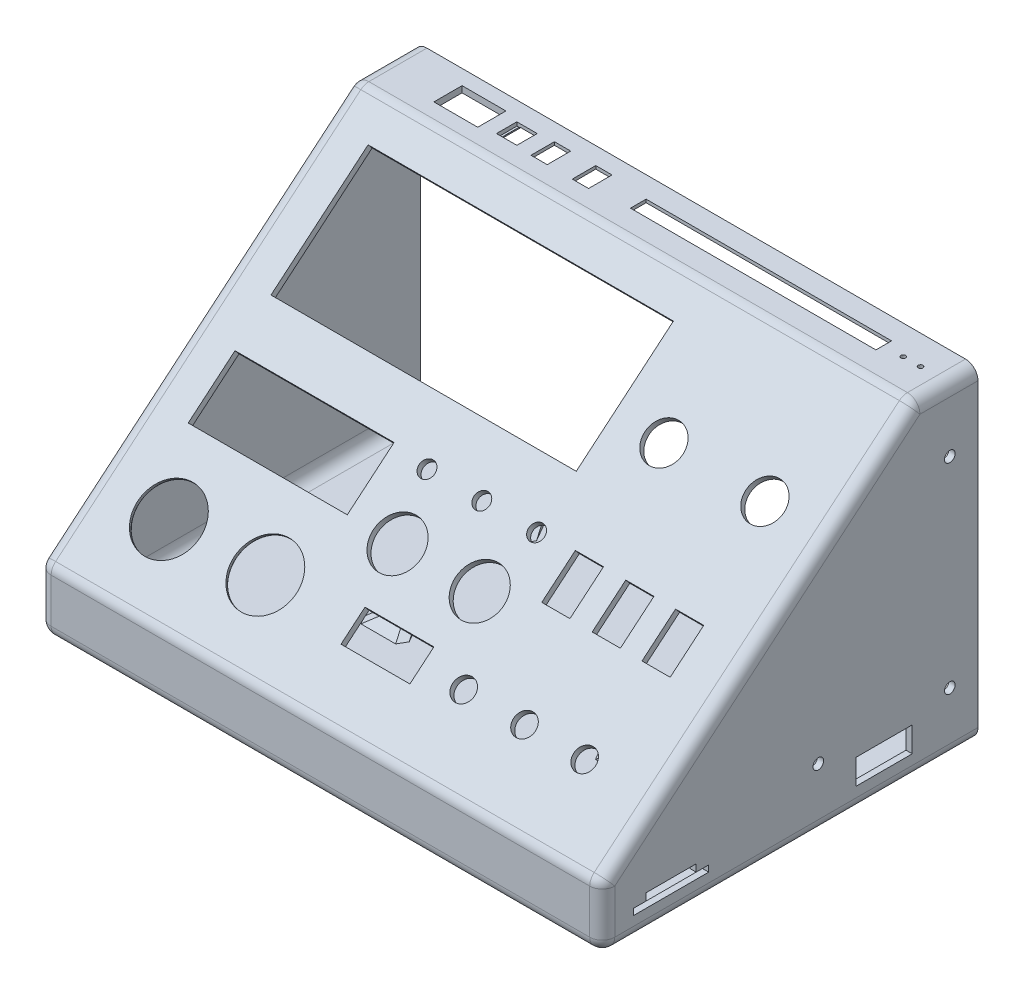
SolidWorks part; units mm, degrees
ref_plane "Front Plane" through (0, 0, 0) normal (0, 0, 1) x (1, 0, 0)
ref_plane "Top Plane" through (0, 0, 0) normal (0, 1, 0) x (1, 0, 0)
ref_plane "Right Plane" through (0, 0, 0) normal (1, 0, 0) x (0, 0, -1)
sketch "Sketch1" plane through (0, 0, 0) normal (0, 1, 0) x (1, 0, 0)
  line L1 (-90, -60) -> (90, -60)
  line L2 (-90, -60) -> (-90, 60)
  line L3 (-90, 60) -> (90, 60)
  line L4 (90, -60) -> (90, 60)
  line L5 (-90, -60) -> (90, 60) construction
  line L6 (-90, 60) -> (90, -60) construction
  point P0 (0, 0)
  dimension "D1" = 180
  dimension "D2" = 120
extrude "Boss-Extrude1" add sketch "Sketch1" along normal blind 20
sketch "Sketch2" plane through (-90, 0, 0) normal (-1, 0, 0) x (0, 0, 1)
  line L0 (60, 20) -> (-40, 103.91)
  line L1 (-60, 20) -> (60, 20) construction
  line L2 (60, 20) -> (60, 0) construction
  line L3 (-60, 20) -> (-60, 103.91)
  line L4 (-60, 103.91) -> (-40, 103.91)
  line L5 (-60, 20) -> (60, 20)
  dimension "D1" = 40
  dimension "D2" = 100
extrude "Boss-Extrude2" add sketch "Sketch2" against normal up to surface (180 mm away) up to face at (90, 10, 0)
shell "Shell3" thickness 2 removed face at (0, 51.955, -60)
fillet "Fillet1" radius 4 11 edges at (-90, 10, 60) (90, 10, 60) (0, 0, 60) (0, 20, 60) (-90, 61.955, 10) (0, 103.91, -40) (90, 61.955, 10) (-90, 103.91, -50) (-90, 0, 0) (90, 0, 0) (90, 103.91, -50)
fillet "Fillet2" radius 4 11 edges at (88, 10.5337, 58) (0, 19.0674, 58) (-88, 10.5337, 58) (0, 2, 58) (88, 101.91, -50.364) (0, 101.91, -40.7279) (-88, 101.91, -50.364) (88, 60.4887, 8.636) (88, 2, -1) (-88, 60.4887, 8.636) (-88, 2, -1)
sketch "Sketch7" plane through (0, 103.91, 0) normal (0, 1, 0) x (1, 0, 0)
  line L0 (-86, 60) -> (-86, 41.4559) construction
  line L1 (-86, 41.4559) -> (-86, 50.7279) construction
  line L2 (-86, 50.7279) -> (-56, 50.7279) construction
  line L3 (-56, 46.2279) -> (-56, 55.2279)
  line L4 (-56, 55.2279) -> (-70, 55.2279)
  line L5 (-70, 55.2279) -> (-70, 46.2279)
  line L6 (-70, 46.2279) -> (-56, 46.2279)
  point P9 (-56, 50.7279)
  dimension "D1" = 9
  dimension "D2" = 14
  dimension "D3" = 30
extrude "Cut-Extrude3" cut sketch "Sketch7" against normal up to next
sketch "Sketch8" plane through (0, 41.2807, 34.6386) normal (0, 0.766, 0.6428) x (1, 0, 0)
  line L0 (-86, 95.9779) -> (86, 95.9779) construction
  line L1 (86, 95.9779) -> (86, -31.2417) construction
  line L2 (86, -31.2417) -> (-86, -31.2417) construction
  line L3 (-86, -31.2417) -> (-86, 95.9779) construction
  line L4 (-76, 95.9779) -> (-76, -31.2417)
  line L5 (-86, 85.9779) -> (86, 85.9779)
  line L6 (86, -31.2417) -> (86, 95.9779) construction
  line L7 (-86, -31.2417) -> (86, -31.2417) construction
  line L8 (76, -31.2417) -> (76, 95.9779)
  line L9 (86, -21.2417) -> (-86, -21.2417)
  line L10 (-86, 95.9779) -> (-86, -31.2417) construction
  line L11 (86, 95.9779) -> (-86, 95.9779) construction
  line L12 (-73.5, 95.9779) -> (-73.5, 93.4779)
  line L13 (-76, 85.9779) -> (21.5, 85.9779)
  line L14 (-76, 85.9779) -> (-76, 45.4779)
  line L15 (-76, 45.4779) -> (21.5, 45.4779)
  line L16 (21.5, 85.9779) -> (21.5, 45.4779)
  line L17 (-76, 85.9779) -> (21.5, 85.9779) construction
  line L18 (-27.25, 85.9779) -> (-27.25, 45.4779) construction
  line L19 (-45.177, 65.7279) -> (-9.323, 65.7279)
  circle A0 centre (-73.5, 93.4779) radius 1.35
  circle A1 centre (-73.5, 37.9779) radius 1.35
  circle A2 centre (19, 37.9779) radius 1.35
  circle A3 centre (19, 93.4779) radius 1.35
  point P36 (-27.25, 65.7279)
  dimension "D1" = 10
  dimension "D2" = 10
  dimension "D3" = 10
  dimension "D4" = 10
  dimension "D5" = 97.5
  dimension "D6" = 40.5
  dimension "D7" = 2.5
  dimension "D8" = 2.5
extrude "Boss-Extrude4" add sketch "Sketch8" against normal blind 5 contours A0 | A3 | A2 | A1
extrude "Cut-Extrude4" cut sketch "Sketch8<3>" against normal blind 5 contours L16 L5 L4 L15 region at (-27.25, 95.8676, -30.4155)
sketch "Sketch8<3>" plane through (0, 41.2807, 34.6386) normal (0, 0.766, 0.6428) x (1, 0, 0) same geometry as "Sketch8"
sketch "Sketch9" plane through (0, 41.2807, 34.6386) normal (0, 0.766, 0.6428) x (1, 0, 0)
  line L0 (-76, 85.9779) -> (-76, 30.4779)
  line L1 (-76, 45.4779) -> (21.5, 45.4779) construction
  line L3 (-76, 30.4779) -> (-25.2, 30.4779)
  line L4 (-76, 30.4779) -> (-76, 10.9779)
  line L5 (-76, 10.9779) -> (-25.2, 10.9779)
  line L6 (-25.2, 30.4779) -> (-25.2, 10.9779)
  dimension "D1" = 15
  dimension "D2" = 50.8
  dimension "D3" = 19.5
extrude "Cut-Extrude5" cut sketch "Sketch9" against normal blind 5 contours L6 L3 L4 L5 region at (-50.6, 54.6044, 18.7601)
sketch "Sketch10" plane through (0, 41.2807, 34.6386) normal (0, 0.766, 0.6428) x (1, 0, 0)
  line L0 (-25.2, 30.4779) -> (-25.2, 10.9779) construction
  line L1 (21.5, 45.4779) -> (21.5, 10.9779)
  line L2 (-25.2, 30.4779) -> (21.5, 30.4779) construction
  line L3 (21.5, 30.4779) -> (21.5, 10.9779) construction
  line L4 (21.5, 10.9779) -> (-25.2, 10.9779) construction
  line L5 (-13.525, 28.9779) -> (3.975, 28.9779)
  line L6 (3.975, 28.9779) -> (21.475, 28.9779)
  line L7 (3.975, 28.9779) -> (-13.525, 28.9779) construction
  line L8 (-13.525, 28.9779) -> (-4.775, 28.9779) construction
  line L9 (-4.775, 28.9779) -> (-13.525, 28.9779) construction
  line L10 (-13.525, 28.9779) -> (-9.15, 28.9779) construction
  line L11 (-9.15, 28.9779) -> (-9.15, 10.9779) construction
  line L12 (21.475, 28.9779) -> (3.975, 28.9779) construction
  line L13 (12.725, 28.9779) -> (21.475, 28.9779) construction
  line L14 (21.475, 28.9779) -> (17.1, 28.9779) construction
  line L15 (17.1, 28.9779) -> (17.1, 10.9779) construction
  circle A0 centre (3.975, 28.9779) radius 2.525
  circle A1 centre (-13.525, 28.9779) radius 2.525
  circle A2 centre (21.475, 28.9779) radius 2.525
  circle A3 centre (-9.15, 10.9779) radius 7.75
  circle A4 centre (17.1, 10.9779) radius 7.75
  point P7 (16.4524, 10.9779)
  point P22 (-10.0142, 10.9779)
  dimension "D1" = 18
  dimension "D2" = 35
  dimension "D3" = 17.5
extrude "Cut-Extrude6" cut sketch "Sketch10" against normal blind 5 contours A1 | A0 | A2 | A4 | A3 | A0 | A2 region at (17.1, 48.3372, 26.229) region at (-15.9786, 59.9074, 12.4402) region at (3.975, 59.2185, 13.2612) region at (21.4943, 59.9074, 12.4402) region at (-9.15, 48.3372, 26.229)
sketch "Sketch11" plane through (0, 41.2807, 34.6386) normal (0, 0.766, 0.6428) x (1, 0, 0)
  line L0 (21.5, 85.9779) -> (21.5, 45.4779) construction
  line L1 (86, 95.9779) -> (-86, 95.9779) construction
  line L2 (21.5, 65.7279) -> (86, 65.7279) construction
  line L3 (86, -31.2417) -> (86, 95.9779) construction
  line L4 (86, 65.7279) -> (53.75, 65.7279) construction
  line L5 (53.75, 65.7279) -> (21.5, 65.7279) construction
  line L6 (69.875, 67.1029) -> (69.875, 54.8529)
  line L7 (86, 65.7279) -> (53.75, 65.7279) construction
  line L8 (53.75, 65.7279) -> (86, 65.7279) construction
  line L9 (86, 65.7279) -> (69.875, 65.7279) construction
  line L10 (69.875, 65.7279) -> (69.875, 60.9779) construction
  line L11 (53.75, 65.7279) -> (53.75, 56.7637)
  circle A0 centre (69.875, 60.9779) radius 6.125
  circle A1 centre (37.625, 60.9779) radius 6.125
  dimension "D1" = 12.25
  dimension "D2" = 35
extrude "Cut-Extrude7" cut sketch "Sketch11" against normal blind 5 contours A1 | L6 A0 | L6 A0 region at (72.4745, 80.4766, -12.0732) region at (67.2755, 80.4766, -12.0732) region at (37.625, 80.4766, -12.0732)
sketch "Sketch12" plane through (0, 41.2807, 34.6386) normal (0, 0.766, 0.6428) x (1, 0, 0)
  line L0 (-76, 10.9779) -> (-76, -4.0221)
  line L1 (-76, -31.2417) -> (-76, -16.2417)
  line L2 (-86, -31.2417) -> (86, -31.2417) construction
  line L3 (-76, -4.0221) -> (-76, -16.2417) construction
  line L4 (-25.2, 10.9779) -> (-25.2, -31.2417)
  line L5 (-25.2, 30.4779) -> (-25.2, 10.9779) construction
  line L6 (-25.2, -31.2417) -> (-25.2, -10.1319)
  line L7 (-25.2, -10.1319) -> (-76, -10.1319)
  line L8 (-50.6, -10.1319) -> (-76, -10.1319) construction
  line L9 (-76, -10.1319) -> (-63.3, -10.1319) construction
  line L10 (-63.3, -10.1319) -> (-63.3, -2.7605) construction
  line L11 (-63.3, -2.7605) -> (-63.3, -10.1319) construction
  line L12 (-63.3, -10.1319) -> (-50.6, -10.1319) construction
  line L13 (-50.6, -10.1319) -> (-25.2, -10.1319) construction
  line L14 (-37.9, -10.1319) -> (-37.9, -2.7605) construction
  circle A2 centre (-66, -10.1319) radius 10
  circle A3 centre (-35.2, -10.1319) radius 10
  dimension "D1" = 15
  dimension "D2" = 15
extrude "Cut-Extrude8" cut sketch "Sketch12" against normal blind 5 contours L7 A2 | L7 A3 | L7 A3 | L7 A2 region at (-66, 32.04, 45.6513) region at (-35.2, 37.4961, 39.1489) region at (-35.2, 32.04, 45.6513) region at (-66, 37.4961, 39.1489)
fillet "Fillet4" radius 1.5 2 edges at (-35.2, 26.8081, 48.775) (-66, 26.8081, 48.775)
sketch "Sketch13" plane through (0, 41.2807, 34.6386) normal (0, 0.766, 0.6428) x (1, 0, 0)
  line L0 (-25.2, -10.1319) -> (32.7814, -10.1319)
  line L1 (21.5, 45.4779) -> (21.5, -10.1319)
  line L2 (21.5, -10.1319) -> (-25.2, -10.1319) construction
  line L3 (-25.2, -10.1319) -> (21.5, -10.1319) construction
  line L4 (21.5, -10.1319) -> (-1.85, -10.1319) construction
  line L5 (-25.2, 10.9779) -> (21.5, 10.9779)
  line L6 (-1.85, -10.1319) -> (-1.85, 10.9779) construction
  line L8 (14.8, -5.1319) -> (-7.2, -5.1319)
  line L12 (14.8, -5.1319) -> (-7.2, -15.1319) construction
  line L14 (-7.2, -15.1319) -> (-7.2, -5.1319)
  line L15 (14.8, -15.1319) -> (-7.2, -15.1319)
  line L18 (14.8, -5.1319) -> (14.8, -15.1319)
  circle A0 centre (-35.2, -10.1319) radius 10 construction
  point P11 (-1.85, 0.423)
  dimension "D1" = 18
  dimension "D2" = 10
  dimension "D3" = 5
  dimension "D4" = 22
extrude "Cut-Extrude9" cut sketch "Sketch13" against normal blind 5 contours L8 | L15 L14 | L18 L0 region at (3.8, 36.375, 40.485) region at (3.8, 33.1611, 44.3152)
sketch "Sketch15" plane through (0, 41.2807, 34.6386) normal (0, 0.766, 0.6428) x (1, 0, 0)
  line L0 (21.5, 45.4779) -> (21.9808, 0)
  line L1 (21.5, 45.4779) -> (86, 45.4779) construction
  line L2 (86, -31.2417) -> (86, 95.9779) construction
  line L3 (86, 45.4779) -> (86, 0) construction
  line L4 (86, 0) -> (21.9808, 0) construction
  line L5 (86, 22.739) -> (21.7404, 22.739) construction
  line L6 (53.8702, 22.739) -> (86, 22.739) construction
  line L7 (49.3702, 15.739) -> (58.3702, 15.739)
  line L8 (49.3702, 15.739) -> (49.3702, 29.739)
  line L9 (49.3702, 29.739) -> (58.3702, 29.739)
  line L10 (58.3702, 15.739) -> (58.3702, 29.739)
  line L11 (49.3702, 15.739) -> (58.3702, 29.739) construction
  line L12 (49.3702, 29.739) -> (58.3702, 15.739) construction
  line L13 (86, 22.739) -> (69.9351, 22.739) construction
  line L14 (69.9351, 22.739) -> (69.9351, 40.2733) construction
  line L15 (69.9351, 40.2733) -> (69.9351, 22.739) construction
  line L16 (69.9351, 22.739) -> (53.8702, 22.739) construction
  line L17 (53.8702, 22.739) -> (21.7404, 22.739) construction
  line L18 (21.7404, 22.739) -> (37.8053, 22.739) construction
  line L19 (37.8053, 22.739) -> (37.8053, 31.5062) construction
  line L20 (33.1892, 15.833) -> (42.1892, 15.833)
  line L21 (33.1892, 15.833) -> (33.1892, 29.833)
  line L22 (33.1892, 29.833) -> (42.1892, 29.833)
  line L23 (42.1892, 15.833) -> (42.1892, 29.833)
  line L24 (65.3123, 15.6839) -> (74.3123, 15.6839)
  line L25 (65.3123, 15.6839) -> (65.3123, 29.6839)
  line L26 (65.3123, 29.6839) -> (74.3123, 29.6839)
  line L27 (74.3123, 15.6839) -> (74.3123, 29.6839)
  point P9 (53.8702, 22.739)
  dimension "D1" = 9
  dimension "D2" = 14
extrude "Cut-Extrude11" cut sketch "Sketch15" against normal blind 3.2 contours L24 L27 L26 L25 | L7 L10 L9 L8 | L20 L23 L22 L21 region at (53.8702, 55.897, 17.2196) region at (37.6892, 55.9575, 17.1476) region at (69.8123, 55.8616, 17.2618)
sketch "Sketch16" plane through (0, 41.2807, 34.6386) normal (0, 0.766, 0.6428) x (1, 0, 0)
  line L0 (9.15, 4.8681) -> (9.15, -25.1319) construction
  line L1 (9.15, -25.1319) -> (9.15, -10.1319) construction
  line L2 (9.15, -10.1319) -> (86, -10.1319) construction
  line L3 (86, -31.2417) -> (86, 95.9779) construction
  line L4 (47.575, -10.1319) -> (86, -10.1319) construction
  line L5 (86, -10.1319) -> (47.575, -10.1319) construction
  line L6 (47.575, -10.1319) -> (9.15, -10.1319) construction
  line L7 (47.575, -10.1319) -> (86, -10.1319) construction
  circle A0 centre (66.7875, -10.1319) radius 3.5
  circle A1 centre (47.575, -10.1319) radius 3.5
  circle A2 centre (28.1503, -10.1319) radius 3.5
extrude "Cut-Extrude12" cut sketch "Sketch16" against normal blind 3.2 contours A0 | A2 | A1 region at (66.7875, 34.7681, 42.4001)
sketch "Sketch17" plane through (0, 0, 0) normal (0, -1, 0) x (1, 0, 0)
  line L0 (-86, 56) -> (-78.2218, 48.2218)
  line L1 (0, 0) -> (25.5086, 0)
  line L2 (57.1505, 0) -> (-57.1505, 0) construction
  line L3 (25.5086, 0) -> (0, 0)
  line L4 (0, 0) -> (0, 11.6481)
  line L5 (0, 0) -> (0, -3.057)
  line L6 (0, -3.057) -> (9.4489, -3.057)
  line L7 (0, -1.5285) -> (4.9263, -1.5285)
  circle A0 centre (-78.2218, 48.2218) radius 6
  circle A1 centre (-78.2218, 48.2218) radius 7
  circle A2 centre (78.2218, 48.2218) radius 7
  circle A3 centre (78.2218, 48.2218) radius 6
  circle A4 centre (78.2218, -51.2788) radius 7
  circle A5 centre (78.2218, -51.2788) radius 6
  circle A6 centre (-78.2218, -51.2788) radius 7
  circle A7 centre (-78.2218, -51.2788) radius 6
  dimension "D1" = 11
extrude "Boss-Extrude5" add sketch "Sketch17" along normal blind 0.5 contours A4 A5 | A2 A3 | A1 A0 | A6 A7 region at (-75.6188, 0, 54.5061) region at (71.4198, 0, 48.2218) region at (71.4198, 0, -51.2788) region at (-85.0238, 0, -51.2788)
fillet "Fillet7" radius 0.5 8 edges at (78.2218, -0.5, -58.2788) (78.2218, -0.5, -57.2788) (-78.2218, -0.5, -57.2788) (-78.2218, -0.5, -58.2788) (-78.2218, -0.5, 41.2218) (-78.2218, -0.5, 42.2218) (78.2218, -0.5, 42.2218) (78.2218, -0.5, 41.2218)
sketch "Sketch18" plane through (0, 101.91, 0) normal (0, -1, 0) x (1, 0, 0)
  line L0 (-56, -50.7279) -> (-51, -50.7279)
  line L1 (-56, -55.2279) -> (-56, -46.2279) construction
  line L2 (-51, -50.7279) -> (-51, -44.1838)
  line L3 (-51, -44.1838) -> (-51, -50.7279)
  line L4 (-51, -50.7279) -> (-51, -58)
  line L5 (84, -60) -> (-84, -60) construction
  line L6 (-51, -58) -> (79, -58)
  line L7 (-51, -58) -> (-51, -44.1838)
  line L8 (-51, -44.1838) -> (79, -44.1838)
  line L9 (79, -58) -> (79, -44.1838)
  line L10 (84, -42.1838) -> (-84, -42.1838) construction
  line L11 (84, -60) -> (84, -42.1838) construction
  dimension "D1" = 5
  dimension "D2" = 2
  dimension "D3" = 2
  dimension "D4" = 5
extrude "Cut-Extrude13" cut sketch "Sketch18" against normal blind 1 contours L6 L9 L8 L2 L4 region at (14, 101.91, -51.0919)
fillet "Fillet8" radius 1 4 edges at (-51, 102.91, -51.0919) (14, 102.91, -44.1838) (79, 102.91, -51.0919) (14, 102.91, -58)
sketch "Sketch19" plane through (0, 103.91, 0) normal (0, 1, 0) x (1, 0, 0)
  line L0 (-56, 50.7279) -> (-48, 50.7279)
  line L2 (-46, 50.7279) -> (-35, 50.7279)
  line L3 (-35, 50.7279) -> (-37.4401, 50.7279)
  line L4 (-34.55, 54.4779) -> (-39.75, 54.4779)
  line L5 (-34.55, 54.4779) -> (-34.55, 46.9779)
  line L6 (-34.55, 46.9779) -> (-39.75, 46.9779)
  line L7 (-39.75, 54.4779) -> (-39.75, 46.9779)
  line L8 (-34.55, 54.4779) -> (-39.75, 46.9779) construction
  line L9 (-34.55, 46.9779) -> (-39.75, 54.4779) construction
  line L10 (-29.2247, 50.7279) -> (-9.2247, 50.7279)
  line L14 (-34.1901, 47.4779) -> (-34.1901, 53.9779)
  line L15 (-40.6901, 47.4779) -> (-34.1901, 53.9779) construction
  line L16 (-40.6901, 53.9779) -> (-34.1901, 47.4779) construction
  line L17 (-9.2247, 50.7279) -> (-9.2247, 53.2279)
  line L18 (-9.2247, 53.2279) -> (69.1753, 53.2279)
  line L19 (69.1753, 53.2279) -> (69.1753, 48.2279)
  line L20 (69.1753, 48.2279) -> (-9.2247, 48.2279)
  line L21 (-9.2247, 48.2279) -> (-9.2247, 50.7279)
  line L22 (69.1753, 50.7279) -> (87.1753, 50.7279)
  line L23 (87.1753, 50.7279) -> (69.1753, 50.7279) construction
  line L24 (75.4253, 50.7279) -> (80.9253, 50.7279)
  line L26 (-29.2247, 50.7279) -> (-23.95, 50.7279)
  line L27 (-56, 55.2279) -> (-56, 46.2279) construction
  line L28 (-26.55, 46.9779) -> (-21.35, 46.9779)
  line L29 (-26.55, 46.9779) -> (-26.55, 54.4779)
  line L30 (-26.55, 54.4779) -> (-21.35, 54.4779)
  line L31 (-21.35, 46.9779) -> (-21.35, 54.4779)
  line L32 (-26.55, 46.9779) -> (-21.35, 54.4779) construction
  line L33 (-26.55, 54.4779) -> (-21.35, 46.9779) construction
  line L34 (-56, 46.2279) -> (-56, 55.2279) construction
  line L36 (-51.25, 47.4779) -> (-44.75, 47.4779)
  line L37 (-51.25, 47.4779) -> (-51.25, 53.9779)
  line L38 (-51.25, 53.9779) -> (-44.75, 53.9779)
  line L39 (-44.75, 47.4779) -> (-44.75, 53.9779)
  line L40 (-51.25, 47.4779) -> (-44.75, 53.9779) construction
  line L41 (-51.25, 53.9779) -> (-44.75, 47.4779) construction
  circle A0 centre (75.4253, 50.7279) radius 0.75
  circle A1 centre (80.9253, 50.7279) radius 0.75
  point P25 (78.1753, 50.7279)
  dimension "D12" = 9
  dimension "D2" = 3.75
  dimension "D3" = 5.2
  dimension "D4" = 21
  dimension "D5" = 6.5
  dimension "D6" = 6.5
  dimension "D8" = 5
  dimension "D9" = 2.5
  dimension "D10" = 78.4
  dimension "D11" = 5.5
  dimension "D13" = 5.2
  dimension "D14" = 3.75
  dimension "D15" = 6.5
  dimension "D16" = 6.5
  dimension "D17" = 8
  dimension "D18" = 5
  dimension "D19" = 8
  dimension "D20" = 12.1253
extrude "Cut-Extrude14" cut sketch "Sketch19" against normal blind 1.2 contours L21 L20 L19 L18 L17 | L14 | L2 L7 L6 L5 L3 | L4 L7 L2 L3 L5 | A0 | A1 | L37 L36 L39 L38 | L29 L28 L31 L30 region at (-39.6587, 103.91, -52.6029) region at (29.9753, 103.91, -50.7279)
sketch "Sketch20" plane through (-90, 0, 0) normal (-1, 0, 0) x (0, 0, 1)
  line L0 (-60, 99.91) -> (-45, 99.91)
  line L1 (-41.4559, 99.91) -> (-60, 99.91) construction
  line L2 (-45, 99.91) -> (-45, 84.91)
  line L3 (-45, 84.91) -> (-60, 84.91)
  line L4 (-60, 99.91) -> (-60, 4) construction
  line L5 (-60, 84.91) -> (-60, 99.91)
  line L6 (-60, 99.91) -> (-41.4559, 99.91) construction
  line L7 (-52.5, 99.91) -> (-52.5, 84.91)
  circle A0 centre (-52.5, 92.41) radius 6
  dimension "D1" = 15
  dimension "D2" = 15
extrude "Cut-Extrude15" cut sketch "Sketch20" against normal blind 10 contours L7 A0 | L7 A0 region at (-90, 92.41, -49.9535) region at (-90, 92.41, -55.0465)
sketch "Sketch21" plane through (0, 0, -60) normal (0, 0, -1) x (-1, 0, 0)
  line L0 (-83, 101.91) -> (-84, 101.91)
  line L1 (-84, 101.91) -> (84, 101.91) construction
  line L2 (-88, 97.91) -> (-88, 96.91)
  line L3 (-88, 97.91) -> (-88, 6) construction
  line L4 (-88, 96.91) -> (-88, 97.91)
  line L5 (-83, 101.91) -> (-83, 96.91)
  line L6 (-83, 96.91) -> (-88, 96.91)
  arc A0 (-88, 97.91) -> (-84, 101.91) centre (-84, 97.91) cw
  line M13 (-88, 6) -> (-88, 97.91)
  arc M14 (-88, 97.91) -> (-84, 101.91) centre (-84, 97.91) cw
  line M15 (-84, 101.91) -> (84, 101.91)
  dimension "D1" = 1
  dimension "D2" = 1
extrude "Boss-Extrude6" add sketch "Sketch21" against normal up to next contours L6 L5 M15 M14 M13 region at (85.2442, 99.1542, -60)
sketch "Sketch22" plane through (0, 0, -60) normal (0, 0, -1) x (-1, 0, 0)
  line L0 (-83, 96.91) -> (-85.5456, 99.4555)
  circle A0 centre (-85.5456, 99.4555) radius 1.6
  dimension "D1" = 3.6
extrude "Cut-Extrude16" cut sketch "Sketch22" against normal blind 16 contours A0 region at (84.1092, 98.8606, -60)
fillet "Fillet9" radius 1 1 edges at (83, 96.91, -47.3846)
sketch "Sketch4" plane through (0, 2, 0) normal (0, 1, 0) x (1, 0, 0)
  line L0 (-84, -54) -> (84, -54) construction
  line L1 (0, -54) -> (0, 60) construction
  line L2 (84, 60) -> (-84, 60) construction
  line L3 (0, -54) -> (0, 60) construction
  line L5 (41.275, 50) -> (-41.275, 50)
  line L6 (41.275, 50) -> (41.275, 1.74)
  line L7 (41.275, 1.74) -> (-41.275, 1.74)
  line L8 (-41.275, 50) -> (-41.275, 1.74)
  line L9 (41.275, 50) -> (-41.275, 1.74) construction
  line L10 (41.275, 1.74) -> (-41.275, 50) construction
  line L15 (38.0996, 1.74) -> (39.6873, -1.01)
  line L16 (39.6873, -1.01) -> (42.8627, -1.01)
  line L17 (42.8627, -1.01) -> (44.4504, 1.74)
  line L18 (44.4504, 1.74) -> (42.8627, 4.49)
  line L25 (42.8627, 4.49) -> (39.6873, 4.49)
  line L44 (39.6873, 4.49) -> (38.0996, 1.74)
  line L45 (38.0996, 50) -> (39.6873, 47.25)
  line L46 (39.6873, 47.25) -> (42.8627, 47.25)
  line L47 (42.8627, 47.25) -> (44.4504, 50)
  line L48 (44.4504, 50) -> (42.8627, 52.75)
  line L49 (42.8627, 52.75) -> (39.6873, 52.75)
  line L50 (39.6873, 52.75) -> (38.0996, 50)
  line L51 (-38.0996, 50) -> (-39.6873, 52.75)
  line L52 (-39.6873, 52.75) -> (-42.8627, 52.75)
  line L53 (-42.8627, 52.75) -> (-44.4504, 50)
  line L54 (-44.4504, 50) -> (-42.8627, 47.25)
  line L55 (-42.8627, 47.25) -> (-39.6873, 47.25)
  line L56 (-39.6873, 47.25) -> (-38.0996, 50)
  line L57 (-30.4796, 1.74) -> (-32.0673, 4.49)
  line L58 (-32.0673, 4.49) -> (-35.2427, 4.49)
  line L59 (-35.2427, 4.49) -> (-36.8304, 1.74)
  line L60 (-36.8304, 1.74) -> (-35.2427, -1.01)
  line L61 (-35.2427, -1.01) -> (-32.0673, -1.01)
  line L62 (-32.0673, -1.01) -> (-30.4796, 1.74)
  circle A1 centre (41.275, 1.74) radius 2.75 construction
  circle A2 centre (41.275, 50) radius 2.75 construction
  circle A3 centre (-41.275, 50) radius 2.75 construction
  circle A4 centre (-33.655, 1.74) radius 2.75 construction
  point P8 (0.5325, 6.382)
  dimension "D1" = 82.55
  dimension "D2" = 48.26
  dimension "D3" = 74.93
  dimension "D4" = 10
extrude "Boss-Extrude7" add sketch "Sketch4" along normal blind 2.5 contours L54 L55 L8 L5 L51 L52 L53 | L61 L62 L7 L60 | L58 L59 L7 L57 | L25 L44 L7 L6 | L18 L25 L6 L7 L15 L16 L17 | L49 L50 L5 L6 L46 L47 L48 | L45 L46 L6 L5 | L55 L56 L5 L8 region at (40.0401, 2, -48.7778) region at (41.6866, 2, -50.4074) region at (-40.0401, 2, -48.7778) region at (-41.6866, 2, -50.4074) region at (41.6866, 2, -1.3326) region at (40.0401, 2, -2.9622) region at (-33.655, 2, -0.5178) region at (-33.655, 2, -2.9622)
sketch "Sketch23" plane through (0, 4.5, 0) normal (0, 1, 0) x (1, 0, 0)
  line L0 (42.8627, -1.01) -> (39.6873, 4.49) construction
  line L1 (38.0996, 1.74) -> (-30.4796, 1.74) construction
  line L2 (-38.0996, 50) -> (38.0996, 50) construction
  line L3 (-38.0996, 50) -> (-39.6873, 52.75) construction
  line L4 (38.0996, 50) -> (0, 50) construction
  line L5 (3.81, 1.74) -> (3.81, 50) construction
  line L6 (15.6177, 25.87) -> (-7.9977, 25.87)
  line L7 (0, 50) -> (0, 19.7968)
  line L8 (38.0996, 50) -> (-38.0996, 50) construction
  line L9 (-39.6873, 47.25) -> (-42.8627, 52.75) construction
  line L10 (42.8627, 47.25) -> (39.6873, 52.75) construction
  circle A0 centre (41.275, 1.74) radius 1.6
  circle A1 centre (-33.655, 1.74) radius 1.6
  circle A2 centre (41.275, 50) radius 1.6
  circle A3 centre (-41.275, 50) radius 1.6
  point P23 (3.81, 25.87)
  point P32 (41.275, 50)
extrude "Cut-Extrude17" cut sketch "Sketch23" against normal blind 3 contours A3 | A2 | A0 | A1 region at (-41.275, 4.5, -50)
chamfer "Chamfer1" distance 2.5 angle 70 12 edges at (43.6566, 2, -0.365) (38.8934, 2, -0.365) (41.275, 2, 1.01) (43.6566, 2, -48.625) (41.275, 2, -47.25) (38.8934, 2, -48.625) (-31.2734, 2, -0.365) (-36.0366, 2, -0.365) (-33.655, 2, 1.01) (-43.6566, 2, -48.625) (-41.275, 2, -47.25) (-38.8934, 2, -48.625) first distance on face at (43.6566, 3.25, -0.365) first distance on face at (38.8934, 3.25, -0.365) first distance on face at (41.275, 3.25, 1.01) first distance on face at (43.6566, 3.25, -48.625) first distance on face at (41.275, 3.25, -47.25) first distance on face at (38.8934, 3.25, -48.625) first distance on face at (-31.2734, 3.25, -0.365) first distance on face at (-36.0366, 3.25, -0.365) first distance on face at (-33.655, 3.25, 1.01) first distance on face at (-43.6566, 3.25, -48.625) first distance on face at (-41.275, 3.25, -47.25) first distance on face at (-38.8934, 3.25, -48.625)
sketch "Sketch25" plane through (88, 0, 0) normal (-1, 0, 0) x (0, 0, 1)
  line L0 (54, 6) -> (50, 6)
  line L1 (-60, 6) -> (54, 6) construction
  line L2 (50, 6) -> (50, 7)
  line L3 (50, 7) -> (26, 7)
  line L4 (26, 7) -> (26, 9)
  line L5 (26, 9) -> (30, 9)
  line L6 (30, 9) -> (30, 11.3)
  line L7 (30, 11.3) -> (46, 11.3)
  line L8 (46, 11.3) -> (46, 9)
  line L9 (46, 9) -> (50, 9)
  line L10 (50, 9) -> (50, 7)
  point P5 (50, 8)
  dimension "D1" = 24
  dimension "D2" = 4
  dimension "D3" = 4
  dimension "D4" = 2
  dimension "D5" = 2.3
  dimension "D6" = 4
  dimension "D7" = 1
  dimension "D8" = 2
extrude "Cut-Extrude18" cut sketch "Sketch25" against normal blind 3 contours L3 L4 L5 L6 L7 L8 L9 L10
sketch "Sketch26" plane through (88, 0, 0) normal (-1, 0, 0) x (0, 0, 1)
  line L0 (-60, 96.91) -> (-60, 6) construction
  line L1 (-60, 51.455) -> (-30, 51.455)
  line L2 (-55, 16.455) -> (-51, 16.455)
  line L3 (-55, 16.455) -> (-5, 16.455)
  line L4 (-55, 16.455) -> (-55, 86.455)
  line L5 (-55, 86.455) -> (-5, 86.455)
  line L6 (-5, 16.455) -> (-5, 86.455)
  line L7 (-55, 16.455) -> (-5, 86.455) construction
  line L8 (-55, 86.455) -> (-5, 16.455) construction
  line L9 (-51, 16.455) -> (-51, 19.455)
  line L10 (-30, 16.455) -> (-30, 25.2168)
  line L11 (-30, 16.455) -> (-30, 6) construction
  line L12 (-60, 6) -> (54, 6) construction
  line L14 (-39, 15.2275) -> (-21, 15.2275)
  line L15 (-39, 15.2275) -> (-39, 7.2275)
  line L16 (-39, 7.2275) -> (-21, 7.2275)
  line L17 (-21, 15.2275) -> (-21, 7.2275)
  line L18 (-39, 15.2275) -> (-21, 7.2275) construction
  line L19 (-39, 7.2275) -> (-21, 15.2275) construction
  circle A0 centre (-51, 19.455) radius 1.7
  circle A1 centre (-9, 19.455) radius 1.7
  circle A2 centre (-51, 83.455) radius 1.7
  point P17 (-30, 11.2275)
  dimension "D6" = 18
  dimension "D1" = 50
  dimension "D2" = 70
  dimension "D3" = 30
  dimension "D4" = 3
  dimension "D5" = 4
  dimension "D7" = 8
extrude "Cut-Extrude19" cut sketch "Sketch26" against normal blind 10 contours A0 | A1 | L17 L14 L15 L16 | A2 region at (88, 20.6231, -52.1681) region at (88, 11.2275, -30) region at (88, 19.455, -9)
